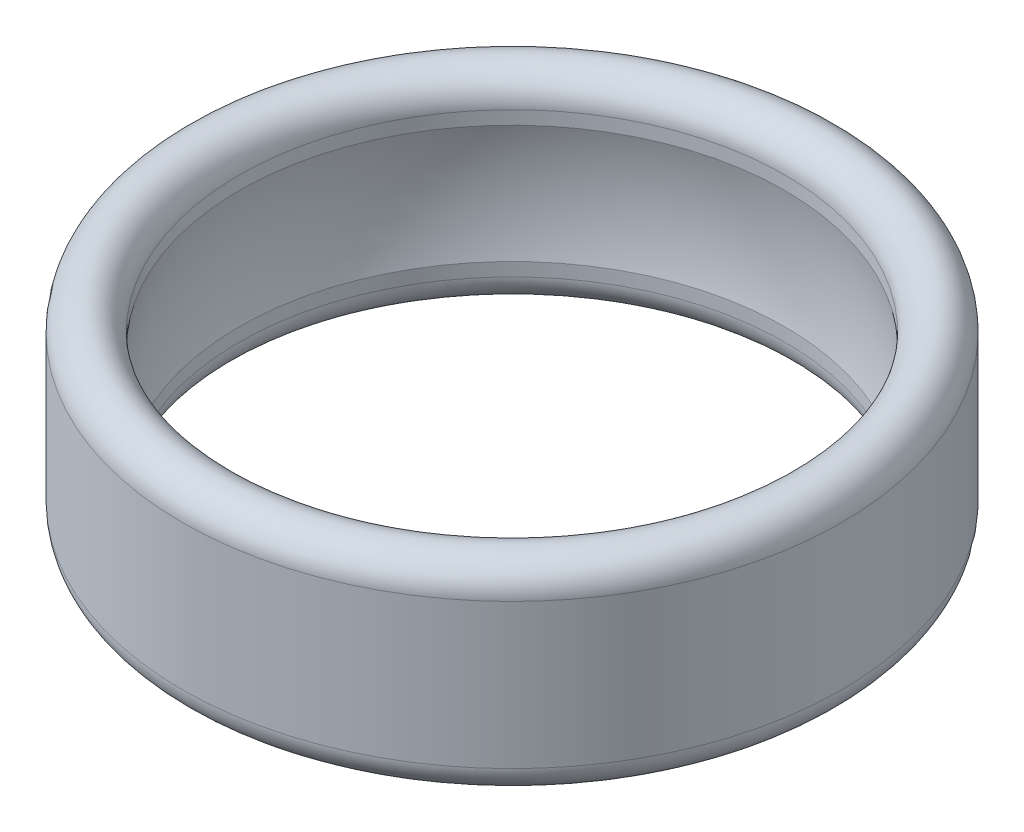
SolidWorks part; units mm, degrees
material "Plain Carbon Steel"
ref_plane "Front Plane" through (0, 0, 0) normal (0, 0, 1) x (1, 0, 0)
ref_plane "Top Plane" through (0, 0, 0) normal (0, 1, 0) x (1, 0, 0)
ref_plane "Right Plane" through (0, 0, 0) normal (1, 0, 0) x (0, 0, -1)
sketch "Sketch2" plane through (0, 0, 0) normal (0, 1, 0) x (1, 0, 0)
  circle A0 centre (0, 0) radius 6.477
  dimension "D1" = 12.954
extrude "Boss-Extrude1" add sketch "Sketch2" along normal blind 3.9624
sketch "Sketch3" plane through (0, 3.9624, 0) normal (0, 1, 0) x (1, 0, 0)
  circle A0 centre (0, 0) radius 5.3594
  dimension "D1" = 10.7188
extrude "Cut-Extrude1" cut sketch "Sketch3" against normal blind 3.9624
sketch "Sketch5" plane through (0, 0, 0) normal (0, 0, 1) x (1, 0, 0)
  line L0 (-5.1068, 3.9624) -> (-5.1068, 0)
  line L1 (-6.477, 0) -> (6.477, 0) construction
  line L2 (6.477, 3.9624) -> (-6.477, 3.9624) construction
  line L3 (0, 0) -> (0, -2.122) construction
  line L4 (5.3594, 3.9624) -> (-5.3594, 3.9624) construction
  arc A1 (-5.1068, 3.9624) -> (-5.1068, 0) centre (-0.127, 1.9812) ccw
  dimension "D2" = 0.127
  dimension "D1" = 5.3594
fillet "Fillet1" 2 edges at (0, 3.9624, 5.3594) (0, 3.9624, 6.477) type full round first side face at (0, 0, 5.3594) second side face at (0, 3.9624, 6.477) middle face at (0, 3.9624, 5.3594)
fillet "Fillet2" 2 edges at (0, 0, 6.477) (0, 0, 5.3594) type full round first side face at (0, 3.4036, 6.477) second side face at (0, 3.4036, 5.3594) middle face at (0, 0, 5.3594)
revolve "Cut-Revolve3" cut sketch "Sketch5" angle 360 about L3
ref_plane "Plane1" through (0, 3.9624, 0) normal (0, 1, 0) x (1, 0, 0)
